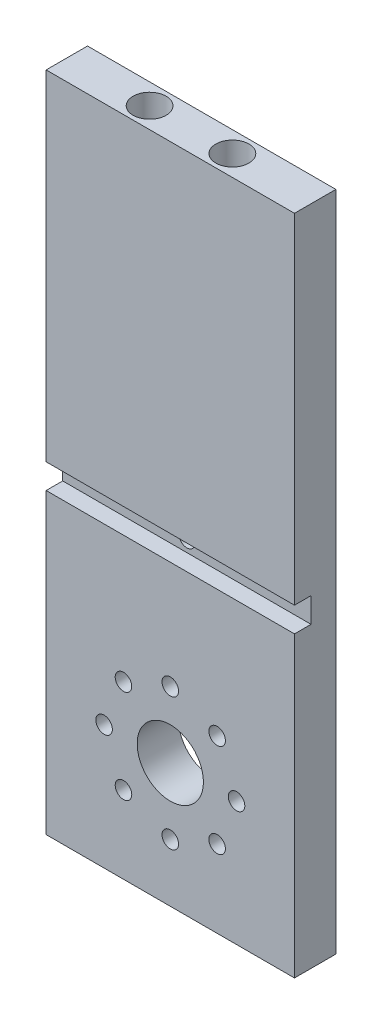
SolidWorks part; units mm, degrees
material "1060 Alloy"
ref_plane "Front Plane" through (0, 0, 0) normal (0, 0, 1) x (1, 0, 0)
ref_plane "Top Plane" through (0, 0, 0) normal (0, 1, 0) x (1, 0, 0)
ref_plane "Right Plane" through (0, 0, 0) normal (1, 0, 0) x (0, 0, -1)
sketch "Sketch1" plane through (0, 0, 0) normal (0, 1, 0) x (1, 0, 0)
  line L1 (-15, 2.5) -> (15, 2.5)
  line L2 (-15, 2.5) -> (-15, -2.5)
  line L3 (-15, -2.5) -> (15, -2.5)
  line L4 (15, 2.5) -> (15, -2.5)
  line L5 (-15, 2.5) -> (15, -2.5) construction
  line L6 (-15, -2.5) -> (15, 2.5) construction
  point P0 (0, 0)
  dimension "D1" = 5
  dimension "D2" = 30
extrude "Boss-Extrude1" add sketch "Sketch1" along normal blind 80 contours L1 L4 L3 L2
sketch "Sketch2" plane through (0, 80, 0) normal (0, 1, 0) x (1, 0, 0)
  line L0 (-5, 0) -> (5, 0) construction
  line L3 (0, 2.5) -> (0, -2.5) construction
  line L4 (-15, 2.5) -> (15, 2.5) construction
  line L5 (-15, -2.5) -> (15, -2.5) construction
  circle A0 centre (-5, 0) radius 2
  circle A1 centre (5, 0) radius 2
  point P10 (0, 0)
  dimension "D1" = 4
  dimension "D2" = 4
  dimension "D3" = 10
extrude "Cut-Extrude1" cut sketch "Sketch2" against normal blind 10
sketch "Sketch3" plane through (0, 0, 2.5) normal (0, 0, 1) x (1, 0, 0)
  line L0 (0, 80) -> (0, 0) construction
  line L1 (-15, 80) -> (15, 80) construction
  line L2 (-15, 0) -> (15, 0) construction
  line L6 (15, 80) -> (15, 0) construction
  circle A6 centre (0, 15) radius 8
  circle A7 centre (0, 23) radius 1
  circle A8 centre (5.6569, 20.6569) radius 1
  circle A9 centre (0, 15) radius 8
  circle A10 centre (8, 15) radius 1
  circle A11 centre (0, 15) radius 8
  circle A12 centre (5.6569, 9.3431) radius 1
  circle A13 centre (0, 15) radius 8
  circle A14 centre (0, 7) radius 1
  circle A15 centre (0, 15) radius 8
  circle A16 centre (-5.6569, 9.3431) radius 1
  circle A17 centre (0, 15) radius 8
  circle A18 centre (-8, 15) radius 1
  circle A19 centre (0, 15) radius 8
  circle A20 centre (-5.6569, 20.6569) radius 1
  circle A21 centre (0, 15) radius 8
  circle A22 centre (0, 15) radius 4
  point P47 (0, 15)
  dimension "D1" = 16
  dimension "D2" = 15
  dimension "D3" = 15
  dimension "D8" = 2
  dimension "D10" = 8
  dimension "D9" = 8
sketch "Sketch4" plane through (0, 0, 2.5) normal (0, 0, 1) x (1, 0, 0)
  line L0 (0, 80) -> (0, 0) construction
  circle A0 centre (0, 30) radius 1
  circle A1 centre (0, 0) radius 1
  dimension "D1" = 2
  dimension "D2" = 2
  dimension "D3" = 30
  dimension "D4" = 15
extrude "Cut-Extrude3" cut sketch "Sketch3" against normal through all contours A19 A20 | A19 A20 | L0 A7 A21 | A7 L0 A6 | A6 L0 A7 | L0 A21 A7 | A6 A8 | A6 A8 | A9 A10 | A9 A10 | A11 A12 | A11 A12 | A14 L0 A21 | A21 L0 A14 | L0 A13 A14 | L0 A14 A13 | A15 A16 | A15 A16 | A17 A18 | A17 A18 | L0 A22 | A22 L0 region at (0.4328, 23.413, 2.5) region at (-0.4328, 23.413, 2.5) region at (0.4155, 22.5645, 2.5) region at (-0.4155, 22.5645, 2.5) region at (-5.3489, 20.3489, 2.5) region at (-5.9489, 20.9489, 2.5) region at (1.6977, 15, 2.5) region at (-1.6977, 15, 2.5) region at (5.9489, 20.9489, 2.5) region at (5.3489, 20.3489, 2.5) region at (-7.5645, 15, 2.5) region at (-8.413, 15, 2.5) region at (0.4155, 7.4355, 2.5) region at (-0.4155, 7.4355, 2.5) region at (8.413, 15, 2.5) region at (7.5645, 15, 2.5) region at (0.4328, 6.587, 2.5) region at (-0.4328, 6.587, 2.5) region at (-5.3489, 9.6511, 2.5) region at (-5.9489, 9.0511, 2.5) region at (5.3489, 9.6511, 2.5) region at (5.9489, 9.0511, 2.5)
sketch "Sketch5" plane through (0, 0, 2.5) normal (0, 0, 1) x (1, 0, 0)
  line L0 (-15, 80) -> (-15, 0) construction
  line L1 (-15, 39) -> (15, 39)
  line L2 (-15, 39) -> (-15, 36)
  line L3 (-15, 36) -> (15, 36)
  line L4 (15, 39) -> (15, 36)
  line L5 (15, 80) -> (15, 0) construction
  line L6 (-15, 0) -> (15, 0) construction
  dimension "D1" = 39
  dimension "D2" = 3
extrude "Cut-Extrude4" cut sketch "Sketch5" against normal blind 2
sketch "Sketch6" plane through (0, 0, 0.5) normal (0, 0, 1) x (1, 0, 0)
  line L0 (-15, 37.5) -> (15, 37.5) construction
  line L1 (-15, 39) -> (-15, 36) construction
  line L2 (15, 36) -> (15, 39) construction
  line L3 (0, 39) -> (0, 36) construction
  line L4 (15, 39) -> (-15, 39) construction
  line L5 (-15, 36) -> (15, 36) construction
  circle A0 centre (0, 37.5) radius 1
  point P8 (0, 42.5)
  dimension "D1" = 2
extrude "Cut-Extrude5" cut sketch "Sketch6" against normal through all contours A0
